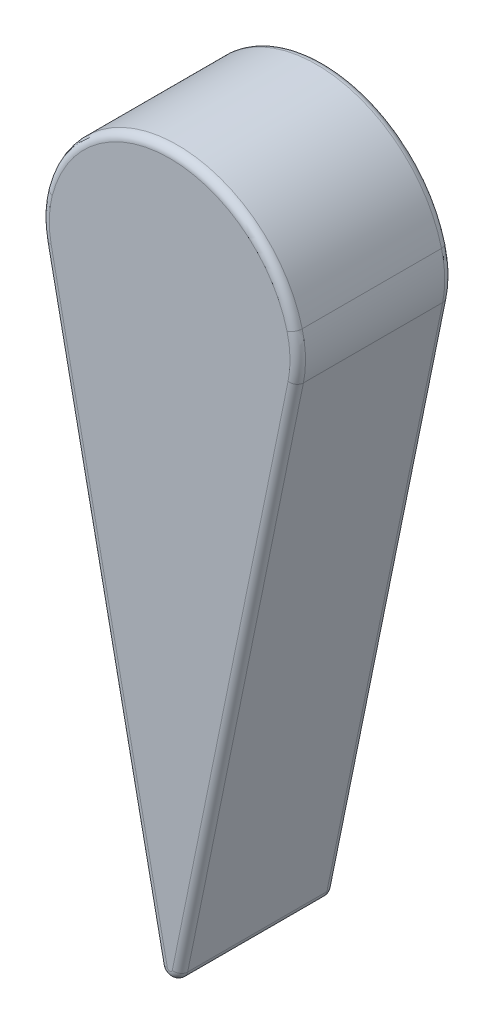
SolidWorks part; units mm, degrees
ref_plane "Front" through (0, 0, 0) normal (0, 0, 1) x (1, 0, 0)
ref_plane "Top" through (0, 0, 0) normal (0, 1, 0) x (1, 0, 0)
ref_plane "Right" through (0, 0, 0) normal (1, 0, 0) x (0, 0, -1)
sketch "Sketch1" plane through (0, 0, 0) normal (0, 0, 1) x (1, 0, 0)
  line L0 (-0.5, 0) -> (0.0007, -2.4496)
  line L1 (0.0007, -2.4496) -> (0.5, 0)
  circle A0 centre (0, 0) radius 0.5
  dimension "D1" = 2.4496
extrude "Boss-Extrude1" add sketch "Sketch1" along normal blind 0.6 contours L1 A0 L0 | A0 L0 L1 region at (0, 0.0003, 0) region at (0.0003, -1.0985, 0)
fillet "Fillet1" radius 0.04 1 edges at (0.0007, -2.4496, 0.3)
fillet "Fillet2" radius 0.4 2 edges at (0.5, 0, 0.3) (-0.5, 0, 0.3)
fillet "Fillet3" radius 0.03 12 edges at (-0.4967, 0.0351, 0) (-0.2637, -1.1564, 0) (0.0006, -2.2896, 0) (0.2643, -1.1563, 0) (0.4967, 0.035, 0) (0.0002, 0.5, 0) (0.0006, -2.2896, 0.6) (-0.2637, -1.1564, 0.6) (-0.4967, 0.0351, 0.6) (0.0002, 0.5, 0.6) (0.4967, 0.035, 0.6) (0.2643, -1.1563, 0.6)
sketch "Sketch2" plane through (0, 0, 0.6) normal (0, 0, 1) x (1, 0, 0)
  line L0 (0.0002, 0.47) -> (0, 0)
  arc A0 (0.4552, 0.117) -> (-0.4551, 0.1173) centre (0, 0) ccw construction
ref_plane "Plane1" through (0, 0, 0) normal (-1, 0.0003, 0) x (0, 0, 1)
sketch "Sketch3" plane through (0, 0, 0) normal (0, 0, -1) x (-1, 0, 0)
  line L2 (0.0092, -2.2516) -> (0.4593, -0.0491)
  line L3 (-0.4594, -0.049) -> (-0.0104, -2.2516)
  line L4 (0.0092, -2.2516) -> (0.4593, -0.0491)
  line L5 (-0.4594, -0.049) -> (-0.0104, -2.2516)
  line L6 (0.1751, -1.409) -> (0.2814, -0.2195)
  line L7 (-0.2812, -0.2197) -> (-0.1742, -1.4091)
  line L8 (0.1751, -1.409) -> (0.2814, -0.2195)
  line L9 (-0.2812, -0.2197) -> (-0.1742, -1.4091)
  circle A1 centre (0, 0) radius 0.3569
  circle A2 centre (0, 0) radius 0.3569
  circle A3 centre (0.0002, -0.6115) radius 0.0533
  arc A4 (0.4593, -0.0491) -> (0.4551, 0.1173) centre (0.0968, 0.025) ccw
  arc A5 (0.4551, 0.1173) -> (-0.4552, 0.117) centre (0, 0) ccw
  arc A6 (-0.4552, 0.117) -> (-0.4594, -0.049) centre (-0.0969, 0.0249) ccw
  arc A7 (-0.0104, -2.2516) -> (0.0092, -2.2516) centre (-0.0006, -2.2496) ccw
  arc A8 (0.4593, -0.0491) -> (0.4551, 0.1173) centre (0.0968, 0.025) ccw
  arc A9 (0.4551, 0.1173) -> (-0.4552, 0.117) centre (0, 0) ccw
  arc A10 (-0.4552, 0.117) -> (-0.4594, -0.049) centre (-0.0969, 0.0249) ccw
  arc A11 (-0.0104, -2.2516) -> (0.0092, -2.2516) centre (-0.0006, -2.2496) ccw
  arc A12 (-0.2812, -0.2197) -> (0.2814, -0.2195) centre (0, 0) ccw
  arc A13 (-0.1742, -1.4091) -> (0.1751, -1.409) centre (0.0005, -1.4091) ccw
  arc A14 (-0.2812, -0.2197) -> (0.2814, -0.2195) centre (0, 0) ccw
  arc A15 (-0.1742, -1.4091) -> (0.1751, -1.409) centre (0.0005, -1.4091) ccw
  circle A16 centre (0.0002, -0.6115) radius 0.0533
  circle A17 centre (0.0003, -0.7817) radius 0.0533
  circle A18 centre (0.0003, -0.7817) radius 0.0533
  circle A19 centre (0.0003, -0.9519) radius 0.0533
  circle A20 centre (0.0003, -0.9519) radius 0.0533
  circle A21 centre (0.0004, -1.122) radius 0.0533
  circle A22 centre (0.0004, -1.122) radius 0.0533
  circle A23 centre (0.0004, -1.2922) radius 0.0533
  circle A24 centre (0.0004, -1.2922) radius 0.0533
  circle A25 centre (0.0005, -1.4624) radius 0.0533
  circle A26 centre (0.0005, -1.4624) radius 0.0533
  dimension "D1" = 0
  dimension "D2" = 0
  dimension "D3" = 0
  dimension "D4" = 0
  dimension "D5" = 0
  dimension "D6" = 0
  dimension "D7" = 0
  dimension "D8" = 0
  dimension "D9" = 0
